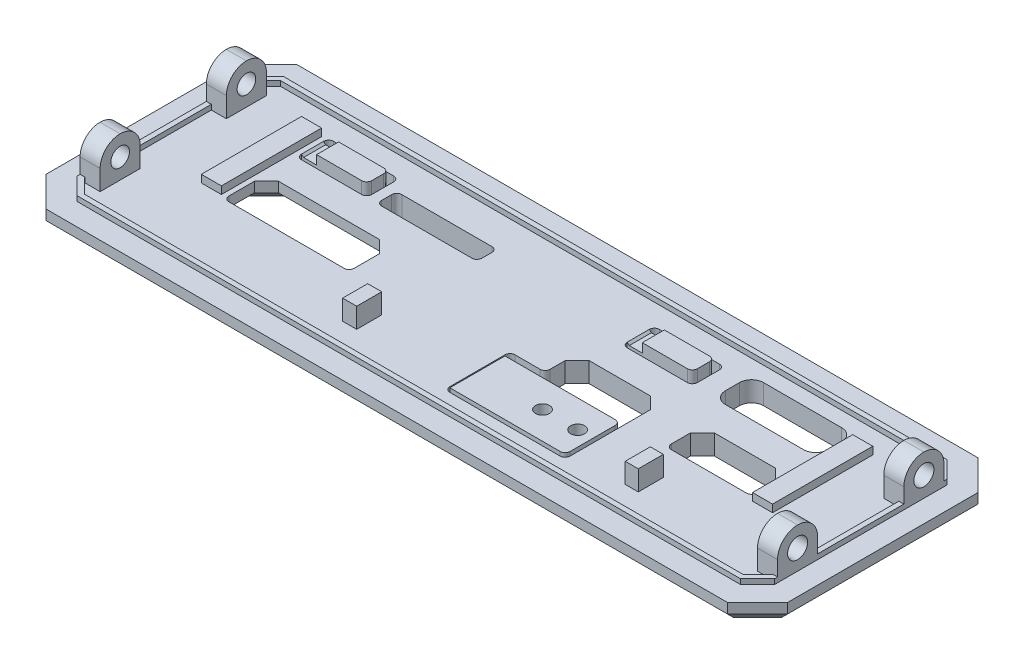
SolidWorks part; units mm, degrees
ref_plane "前视基准面" through (0, 0, 0) normal (0, 0, 1) x (1, 0, 0)
ref_plane "上视基准面" through (0, 0, 0) normal (0, 1, 0) x (1, 0, 0)
ref_plane "右视基准面" through (0, 0, 0) normal (1, 0, 0) x (0, 0, -1)
other "Configuration Table"
sketch "草图2" plane through (0, 0, 0) normal (0, 1, 0) x (1, 0, 0)
  line L0 (-36.7624, 20.764) -> (-33.7624, 23.764)
  line L1 (-36.7624, 1.764) -> (-33.7624, -1.236)
  line L2 (-33.7624, 23.764) -> (34.2376, 23.764)
  line L3 (-36.7624, 20.764) -> (-36.7624, 1.764)
  line L4 (-33.7624, -1.236) -> (34.2376, -1.236)
  line L5 (37.2376, 20.764) -> (37.2376, 1.764)
  line L6 (34.2376, -1.236) -> (37.2376, 1.764)
  line L7 (34.2376, 23.764) -> (37.2376, 20.764)
  point P5 (-36.7624, -1.236)
  point P7 (-36.7624, -1.236)
  point P8 (37.2376, 23.764)
  point P10 (37.2376, 23.764)
  point P11 (37.2376, -1.236)
  point P13 (-36.7624, 23.764)
  point P15 (-36.7624, 23.764)
  dimension "D1" = 74
  dimension "D2" = 25
extrude "凸台-拉伸1" add sketch "草图2" along normal blind 2
chamfer "倒角1" distance 1 angle 45 8 edges at (-36.7624, 0, -11.264) (0.2376, 0, -23.764) (0.2376, 0, 1.236) (37.2376, 0, -11.264) (-35.2624, 0, -22.264) (-35.2624, 0, -0.264) (35.7376, 0, -0.264) (35.7376, 0, -22.264)
sketch "草图3" plane through (0, 0, 0) normal (0, -1, 0) x (1, 0, 0)
  line L1 (-25.7624, -8.514) -> (-13.2624, -8.514)
  line L2 (-25.7624, -8.514) -> (-25.7624, -12.764)
  line L3 (-25.7624, -12.764) -> (-13.2624, -12.764)
  line L4 (-13.2624, -8.514) -> (-13.2624, -12.764)
  line L5 (1.7376, -3.064) -> (13.7376, -3.064)
  line L7 (5.2376, -12.764) -> (13.7376, -12.764)
  line L8 (13.7376, -3.064) -> (13.7376, -12.764)
  line L9 (17.7376, -9.164) -> (26.2376, -9.164)
  line L10 (17.7376, -9.164) -> (17.7376, -12.764)
  line L11 (17.7376, -12.764) -> (26.2376, -12.764)
  line L12 (26.2376, -9.164) -> (26.2376, -12.764)
  line L13 (15.8376, -15.764) -> (26.0376, -15.764)
  line L14 (15.8376, -15.764) -> (15.8376, -19.564)
  line L15 (15.8376, -19.564) -> (26.0376, -19.564)
  line L16 (26.0376, -15.764) -> (26.0376, -19.564)
  line L17 (6.7376, -15.764) -> (13.7376, -15.764)
  line L18 (6.7376, -15.764) -> (6.7376, -18.964)
  line L19 (6.7376, -18.964) -> (13.7376, -18.964)
  line L20 (13.7376, -15.764) -> (13.7376, -18.964)
  line L21 (-25.7624, -15.764) -> (-18.7624, -15.764)
  line L22 (-25.7624, -15.764) -> (-25.7624, -18.964)
  line L23 (-25.7624, -18.964) -> (-18.7624, -18.964)
  line L24 (-18.7624, -15.764) -> (-18.7624, -18.964)
  line L25 (-17.7624, -15.764) -> (-7.7624, -15.764)
  line L26 (-17.7624, -15.764) -> (-17.7624, -17.764)
  line L27 (-17.7624, -17.764) -> (-7.7624, -17.764)
  line L28 (-7.7624, -15.764) -> (-7.7624, -17.764)
  line L29 (-36.7624, -20.764) -> (-36.7624, -1.764) construction
  line L30 (-34.7624, -15.764) -> (-43.2418, -15.764) construction
  line L31 (37.2376, -1.764) -> (37.2376, -20.764) construction
  line L32 (-35.2588, -12.764) -> (-41.1207, -12.764) construction
  line L33 (-33.7624, 1.236) -> (34.2376, 1.236) construction
  line L35 (5.2376, -12.764) -> (5.2376, -9.564)
  line L36 (5.2376, -9.564) -> (1.7376, -9.564)
  line L37 (1.7376, -9.564) -> (1.7376, -3.064)
  dimension "D1" = 14
  dimension "D3" = 12.5
  dimension "D4" = 4.25
  dimension "D5" = 3.2
  dimension "D6" = 2
  dimension "D7" = 7
  dimension "D8" = 11
  dimension "D9" = 1
  dimension "D10" = 10
  dimension "D11" = 23.5
  dimension "D12" = 7
  dimension "D13" = 3.8
  dimension "D14" = 3.6
  dimension "D15" = 11
  dimension "D16" = 11.2
  dimension "D17" = 10.2
  dimension "D18" = 8.5
  dimension "D19" = 12
  dimension "D20" = 6.5
  dimension "D21" = 8.5
  dimension "D22" = 3.2
  dimension "D23" = 29
  dimension "D24" = 3
extrude "切除-拉伸1" cut sketch "草图3" against normal up to next
fillet "圆角1" radius 1.2 4 edges at (26.0376, 1, -15.764) (26.0376, 1, -19.564) (15.8376, 1, -19.564) (15.8376, 1, -15.764)
fillet "圆角2" radius 0.5 20 edges at (-7.7624, 1, -15.764) (-7.7624, 1, -17.764) (-17.7624, 1, -17.764) (-17.7624, 1, -15.764) (-18.7624, 1, -18.964) (-18.7624, 1, -15.764) (-25.7624, 1, -18.964) (-25.7624, 1, -15.764) (6.7376, 1, -18.964) (13.7376, 1, -18.964) (13.7376, 1, -15.764) (6.7376, 1, -15.764) (13.7376, 1, -3.064) (17.7376, 1, -9.164) (26.2376, 1, -9.164) (-13.2624, 1, -8.514) (-25.7624, 1, -8.514) (1.7376, 1, -3.064) (1.7376, 1, -9.564) (5.2376, 1, -9.564)
chamfer "倒角2" distance 1.2 angle 45 6 edges at (26.2376, 1, -12.764) (17.7376, 1, -12.764) (13.7376, 1, -12.764) (-13.2624, 1, -12.764) (-25.7624, 1, -12.764) (5.2376, 1, -12.764)
sketch "草图4" plane through (0, 0, 0) normal (0, -1, 0) x (1, 0, 0)
  line L0 (13.2376, -3.064) -> (2.2376, -3.064) construction
  line L1 (-22.7624, -16.264) -> (-19.2624, -16.264)
  line L2 (-22.7624, -16.264) -> (-22.7624, -18.464)
  line L3 (-22.7624, -18.464) -> (-19.2624, -18.464)
  line L4 (-19.2624, -16.264) -> (-19.2624, -18.464)
  line L5 (6.7376, -3.564) -> (13.2376, -3.564)
  line L6 (6.7376, -3.564) -> (6.7376, -9.064)
  line L7 (6.7376, -9.064) -> (13.2376, -9.064)
  line L8 (13.2376, -3.564) -> (13.2376, -9.064)
  line L9 (8.7376, -16.264) -> (13.2376, -16.264)
  line L10 (8.7376, -16.264) -> (8.7376, -18.464)
  line L11 (8.7376, -18.464) -> (13.2376, -18.464)
  line L12 (13.2376, -16.264) -> (13.2376, -18.464)
  line L13 (13.7376, -11.564) -> (13.7376, -3.564) construction
  line L15 (2.2376, -9.564) -> (4.7376, -9.564) construction
  line L16 (13.7376, -18.464) -> (13.7376, -16.264) construction
  line L17 (7.2376, -18.964) -> (13.2376, -18.964) construction
  line L18 (13.2376, -15.764) -> (7.2376, -15.764) construction
  line L19 (-19.2624, -15.764) -> (-25.2624, -15.764) construction
  line L20 (-25.2624, -18.964) -> (-19.2624, -18.964) construction
  line L21 (-18.7624, -18.464) -> (-18.7624, -16.264) construction
  dimension "D1" = 0.5
  dimension "D2" = 6.5
  dimension "0.5" = 0.5
  dimension "D3" = 0.5
  dimension "D4" = 0.5
  dimension "D5" = 0.5
  dimension "D6" = 0.5
  dimension "D7" = 4.5
  dimension "D8" = 0.5
  dimension "D9" = 0.5
  dimension "D10" = 0.5
  dimension "D11" = 3.5
extrude "凸台-拉伸2" add sketch "草图4" against normal blind 1 separate body
sketch "草图5" plane through (0, 1, 0) normal (0, 1, 0) x (1, 0, 0)
  line L0 (-25.7624, 18.464) -> (-25.7624, 16.264) construction
  line L1 (-19.2624, 16.264) -> (-25.7624, 16.264)
  line L2 (-19.2624, 16.264) -> (-19.2624, 18.464)
  line L3 (-19.2624, 18.464) -> (-25.7624, 18.464)
  line L4 (-25.7624, 16.264) -> (-25.7624, 18.464)
  line L5 (8.7376, 18.464) -> (13.2376, 18.464) construction
  line L6 (13.2376, 16.264) -> (6.7376, 16.264)
  line L7 (13.2376, 16.264) -> (13.2376, 18.464)
  line L8 (13.2376, 18.464) -> (6.7376, 18.464)
  line L9 (6.7376, 16.264) -> (6.7376, 18.464)
extrude "凸台-拉伸3" add sketch "草图5" along normal blind 0.8
sketch "草图16" plane through (0, 1.8, 0) normal (0, 1, 0) x (1, 0, 0)
  line L0 (13.2376, 18.464) -> (6.7376, 18.464) construction
  line L1 (13.2376, 16.264) -> (8.2376, 16.264)
  line L2 (13.2376, 16.264) -> (13.2376, 18.464)
  line L3 (13.2376, 18.464) -> (8.2376, 18.464)
  line L4 (8.2376, 16.264) -> (8.2376, 18.464)
  line L5 (-25.7624, 16.264) -> (-19.2624, 16.264) construction
  line L6 (-19.2624, 18.464) -> (-24.2624, 18.464)
  line L7 (-19.2624, 18.464) -> (-19.2624, 16.264)
  line L8 (-19.2624, 16.264) -> (-24.2624, 16.264)
  line L9 (-24.2624, 18.464) -> (-24.2624, 16.264)
  dimension "D1" = 5
extrude "凸台-拉伸10" add sketch "草图16" along normal blind 0.9
sketch "草图6" plane through (0, 1, 0) normal (0, 1, 0) x (1, 0, 0)
  line L2 (13.2376, 3.564) -> (1.7376, 3.564)
  line L3 (13.2376, 3.564) -> (13.2376, 9.064)
  line L4 (13.2376, 9.064) -> (1.7376, 9.064)
  line L5 (1.7376, 3.564) -> (1.7376, 9.064)
extrude "凸台-拉伸4" add sketch "草图6" along normal blind 0.9
fillet "圆角5" radius 1 3 edges at (6.7376, 1, -17.364) (-25.7624, 1, -17.364) (1.7376, 1, -6.314)
fillet "圆角3" radius 0.5 12 edges at (8.7376, 0.5, -16.264) (8.7376, 0.5, -18.464) (13.2376, 1.35, -18.464) (13.2376, 1.35, -16.264) (-19.2624, 1.35, -16.264) (-19.2624, 1.35, -18.464) (-22.7624, 0.5, -18.464) (-22.7624, 0.5, -16.264) (13.2376, 0.95, -3.564) (6.7376, 0.5, -3.564) (13.2376, 0.95, -9.064) (6.7376, 0.5, -9.064)
chamfer "倒角3" distance 0.2 angle 45 2 edges at (-25.7624, 1.8, -17.364) (6.7376, 1.8, -17.364)
sketch "草图7" plane through (0, 2, 0) normal (0, 1, 0) x (1, 0, 0)
  line L0 (34.2376, -1.236) -> (-33.7624, -1.236) construction
  line L1 (-7.8624, 6.364) -> (-9.2624, 6.364)
  line L2 (-7.8624, 6.364) -> (-7.8624, 3.864)
  line L3 (-7.8624, 3.864) -> (-9.2624, 3.864)
  line L4 (-9.2624, 6.364) -> (-9.2624, 3.864)
  line L5 (20.2376, 3.864) -> (18.9376, 3.864)
  line L6 (20.2376, 3.864) -> (20.2376, 6.364)
  line L7 (20.2376, 6.364) -> (18.9376, 6.364)
  line L8 (18.9376, 3.864) -> (18.9376, 6.364)
  line L9 (37.2376, 1.764) -> (37.2376, 20.764) construction
  line L10 (-36.7624, 1.764) -> (-36.7624, 20.764) construction
  dimension "D1" = 5.1
  dimension "D2" = 17
  dimension "D3" = 27.5
  dimension "D4" = 1.3
  dimension "D5" = 1.4
  dimension "D6" = 2.5
extrude "凸台-拉伸5" add sketch "草图7" along normal blind 2
sketch "草图11" plane through (0, 2, 0) normal (0, 1, 0) x (1, 0, 0)
  line L0 (-33.7624, -1.236) -> (34.2376, -1.236) construction
  line L1 (28.7376, 8.764) -> (26.7376, 8.764)
  line L2 (28.7376, 8.764) -> (28.7376, 18.764)
  line L3 (28.7376, 18.764) -> (26.7376, 18.764)
  line L4 (26.7376, 8.764) -> (26.7376, 18.764)
  line L5 (-26.2624, 8.764) -> (-28.2624, 8.764)
  line L6 (-26.2624, 8.764) -> (-26.2624, 18.764)
  line L7 (-26.2624, 18.764) -> (-28.2624, 18.764)
  line L8 (-28.2624, 8.764) -> (-28.2624, 18.764)
  line L9 (-36.7624, 20.764) -> (-36.7624, 1.764) construction
  line L10 (37.2376, 1.764) -> (37.2376, 20.764) construction
  dimension "D1" = 10
  dimension "D2" = 8.5
  dimension "D3" = 2
  dimension "D4" = 10
  dimension "D5" = 8.5
  dimension "D6" = 2
extrude "凸台-拉伸7" add sketch "草图11" along normal blind 0.75
sketch "草图8" plane through (0, 2, 0) normal (0, 1, 0) x (1, 0, 0)
  line L1 (35.0376, 2.964) -> (33.0376, 2.964)
  line L2 (35.0376, 2.964) -> (35.0376, 6.964)
  line L3 (35.0376, 6.964) -> (33.0376, 6.964)
  line L4 (33.0376, 2.964) -> (33.0376, 6.964)
  line L6 (35.0376, 15.564) -> (33.0376, 15.564)
  line L7 (35.0376, 15.564) -> (35.0376, 19.564)
  line L8 (35.0376, 19.564) -> (33.0376, 19.564)
  line L9 (33.0376, 15.564) -> (33.0376, 19.564)
  line L10 (-34.5624, 2.964) -> (-32.5624, 2.964)
  line L11 (-34.5624, 2.964) -> (-34.5624, 6.964)
  line L12 (-34.5624, 6.964) -> (-32.5624, 6.964)
  line L13 (-32.5624, 2.964) -> (-32.5624, 6.964)
  line L15 (-34.5624, 15.564) -> (-32.5624, 15.564)
  line L16 (-34.5624, 15.564) -> (-34.5624, 19.564)
  line L17 (-34.5624, 19.564) -> (-32.5624, 19.564)
  line L18 (-32.5624, 15.564) -> (-32.5624, 19.564)
  line L21 (-36.7624, 20.764) -> (-36.7624, 1.764) construction
  line L22 (34.2376, 23.764) -> (-33.7624, 23.764) construction
  line L23 (-33.7624, -1.236) -> (34.2376, -1.236) construction
  line L24 (37.2376, 1.764) -> (37.2376, 20.764) construction
  dimension "D1" = 4
  dimension "D2" = 2.2
  dimension "D3" = 4.2
  dimension "D4" = 4.2
  dimension "D5" = 2.2
  dimension "D6" = 2
extrude "凸台-拉伸6" add sketch "草图8" along normal blind 4
fillet "圆角4" radius 2 8 edges at (34.0376, 6, -6.964) (34.0376, 6, -2.964) (34.0376, 6, -19.564) (34.0376, 6, -15.564) (-33.5624, 6, -15.564) (-33.5624, 6, -19.564) (-33.5624, 6, -2.964) (-33.5624, 6, -6.964)
sketch "草图9" plane through (-34.5624, 0, 0) normal (-1, 0, 0) x (0, 0, 1)
  circle A0 centre (-4.964, 4) radius 1
  circle A1 centre (-17.564, 4) radius 1
  dimension "D1" = 2
extrude "切除-拉伸2" cut sketch "草图9" against normal up to next (2 mm away) draft 2
sketch "草图10" plane through (35.0376, 0, 0) normal (1, 0, 0) x (0, 0, -1)
  circle A0 centre (4.964, 4) radius 1
  circle A1 centre (17.564, 4) radius 1
  dimension "D1" = 2
extrude "切除-拉伸3" cut sketch "草图10" against normal up to next (2 mm away) draft 2
sketch "草图14" plane through (0, 0, 0) normal (0, -1, 0) x (1, 0, 0)
  line L0 (7.0755, -6.314) -> (5.3752, -6.314) construction
  line L3 (13.2376, -8.564) -> (13.2376, -4.064) construction
  circle A0 centre (11.7376, -6.314) radius 0.7
  circle A1 centre (8.2376, -6.314) radius 0.7
  point P5 (13.2376, -6.314)
  dimension "D1" = 1.4
  dimension "D2" = 3.5
  dimension "D3" = 1.5
extrude "切除-拉伸4" cut sketch "草图14" against normal up to next
sketch "草图17" plane through (0, 2, 0) normal (0, 1, 0) x (1, 0, 0)
  line L8 (33.1192, 21.064) -> (-32.644, 21.064)
  line L9 (-32.644, 21.064) -> (-34.0624, 19.6456)
  line L10 (-34.0624, 19.6456) -> (-34.0624, 2.8823)
  line L11 (-34.0624, 2.8823) -> (-32.644, 1.464)
  line L12 (-32.644, 1.464) -> (33.1192, 1.464)
  line L13 (33.1192, 1.464) -> (34.5376, 2.8823)
  line L14 (34.5376, 2.8823) -> (34.5376, 19.6456)
  line L15 (34.5376, 19.6456) -> (33.1192, 21.064)
  line L16 (33.3264, 21.564) -> (-32.8511, 21.564)
  line L17 (-32.8511, 21.564) -> (-34.5624, 19.8527)
  line L18 (-34.5624, 19.8527) -> (-34.5624, 2.6752)
  line L19 (-34.5624, 2.6752) -> (-32.8511, 0.964)
  line L20 (-32.8511, 0.964) -> (33.3264, 0.964)
  line L21 (33.3264, 0.964) -> (35.0376, 2.6752)
  line L22 (35.0376, 2.6752) -> (35.0376, 19.8527)
  line L23 (35.0376, 19.8527) -> (33.3264, 21.564)
  line L24 (33.3264, 21.564) -> (-32.8511, 21.564)
  line L25 (-32.8511, 21.564) -> (-34.5624, 19.8527)
  line L26 (-34.5624, 19.8527) -> (-34.5624, 2.6752)
  line L27 (-34.5624, 2.6752) -> (-32.8511, 0.964)
  line L28 (-32.8511, 0.964) -> (33.3264, 0.964)
  line L29 (33.3264, 0.964) -> (35.0376, 2.6752)
  line L30 (35.0376, 2.6752) -> (35.0376, 19.8527)
  line L31 (35.0376, 19.8527) -> (33.3264, 21.564)
  dimension "D1" = 2.2
  dimension "D2" = 0.5
extrude "凸台-拉伸11" add sketch "草图17" along normal blind 0.5
chamfer "倒角6" distance 1 angle 45 8 edges at (-25.7624, 0, -10.289) (-25.6159, 0, -8.6604) (-19.5124, 0, -8.514) (-13.4088, 0, -8.6604) (-25.1624, 0, -12.164) (-19.5124, 0, -12.764) (-13.8624, 0, -12.164) (-13.2624, 0, -10.289)
